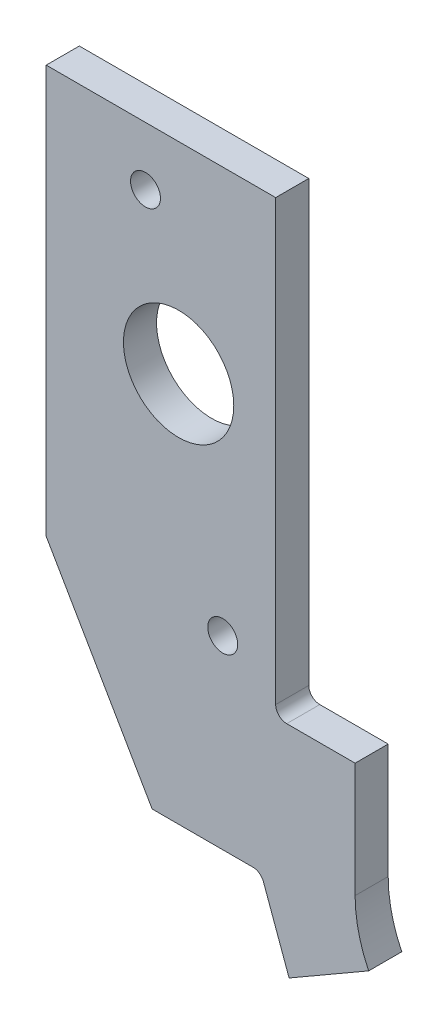
SolidWorks part; units mm, degrees
ref_plane "Front Plane" through (0, 0, 0) normal (0, 0, 1) x (1, 0, 0)
ref_plane "Top Plane" through (0, 0, 0) normal (0, 1, 0) x (1, 0, 0)
ref_plane "Right Plane" through (0, 0, 0) normal (1, 0, 0) x (0, 0, -1)
sketch "Sketch1" plane through (0, 0, 0) normal (0, 0, 1) x (1, 0, 0)
  line L9 (-3163.8864, 1099.0912) -> (-3160.1878, 1088.9294)
  line L10 (-3160.1878, 1088.9294) -> (-3148.7348, 1095.5417)
  line L11 (-3150.6888, 1103.9457) -> (-3150.6888, 1120.4557)
  line L12 (-3150.6888, 1120.4557) -> (-3160.5313, 1120.4557)
  line L13 (-3162.1188, 1122.0432) -> (-3162.1188, 1185.2257)
  line L14 (-3162.1188, 1185.2257) -> (-3195.1388, 1185.2257)
  line L15 (-3195.1388, 1185.2257) -> (-3195.1388, 1126.4882)
  line L16 (-3195.1388, 1126.4882) -> (-3179.8988, 1100.1357)
  line L17 (-3179.8988, 1100.1357) -> (-3165.3781, 1100.1357)
  line L18 (-3163.8864, 1099.0912) -> (-3160.1878, 1088.9294)
  line L19 (-3160.1878, 1088.9294) -> (-3148.7348, 1095.5417)
  line L20 (-3150.6888, 1103.9457) -> (-3150.6888, 1120.4557)
  line L21 (-3150.6888, 1120.4557) -> (-3160.5313, 1120.4557)
  line L22 (-3162.1188, 1122.0432) -> (-3162.1188, 1185.2257)
  line L23 (-3162.1188, 1185.2257) -> (-3195.1388, 1185.2257)
  line L24 (-3195.1388, 1185.2257) -> (-3195.1388, 1126.4882)
  line L25 (-3195.1388, 1126.4882) -> (-3179.8988, 1100.1357)
  line L26 (-3179.8988, 1100.1357) -> (-3165.3781, 1100.1357)
  arc A3 (-3150.6888, 1103.9457) -> (-3148.7348, 1095.5417) centre (-3131.6388, 1103.9457) ccw
  arc A4 (-3162.1188, 1122.0432) -> (-3160.5313, 1120.4557) centre (-3160.5313, 1122.0432) ccw
  arc A5 (-3163.8864, 1099.0912) -> (-3165.3781, 1100.1357) centre (-3165.3781, 1098.5482) ccw
  arc A6 (-3150.6888, 1103.9457) -> (-3148.7348, 1095.5417) centre (-3131.6388, 1103.9457) ccw
  arc A7 (-3162.1188, 1122.0432) -> (-3160.5313, 1120.4557) centre (-3160.5313, 1122.0432) ccw
  arc A8 (-3163.8864, 1099.0912) -> (-3165.3781, 1100.1357) centre (-3165.3781, 1098.5482) ccw
  dimension "D1" = 0
extrude "Boss-Extrude1" add sketch "Sketch1" along normal blind 4.7625
hole_wizard "#6 Clearance Hole1" positions "Sketch3" profile "Sketch2" hole size "#6" standard "ANSI Inch" end condition through all
sketch "Sketch3" plane through (0, 0, 4.7625) normal (0, 0, 1) x (1, 0, 0)
  point P0 (-3169.7388, 1126.8057)
  point P3 (-3180.8513, 1176.8437)
sketch "Sketch2" plane through (-3169.7388, 1126.8057, 4.7625) normal (1, 0, 0) x (0, -1, 0)
  line L0 (0, 0) -> (0, 4.7625)
  line L1 (0, 4.7625) -> (2.1526, 4.7625)
  line L2 (2.1526, 4.7625) -> (2.1526, 0)
  line L5 (2.1526, 0) -> (0, 0)
  line L11 (0, -6.35) -> (0, 107.95) construction
  dimension "Thru Hole Dia." = 4.3053
  dimension "Thru Hole Depth" = 4.7625
hole_wizard "5/8 (0.625) Diameter Hole1" positions "Sketch5" profile "Sketch4" hole size "5/8" standard "ANSI Inch" end condition through all
sketch "Sketch5" plane through (0, 0, 4.7625) normal (0, 0, 1) x (1, 0, 0)
  point P0 (-3176.0888, 1156.2697)
sketch "Sketch4" plane through (-3176.0888, 1156.2697, 4.7625) normal (1, 0, 0) x (0, -1, 0)
  line L0 (0, 0) -> (0, 4.7625)
  line L1 (0, 4.7625) -> (7.9375, 4.7625)
  line L2 (7.9375, 4.7625) -> (7.9375, 0)
  line L5 (7.9375, 0) -> (0, 0)
  line L11 (0, -6.35) -> (0, 107.95) construction
  dimension "Thru Hole Dia." = 15.875
  dimension "Thru Hole Depth" = 4.7625
